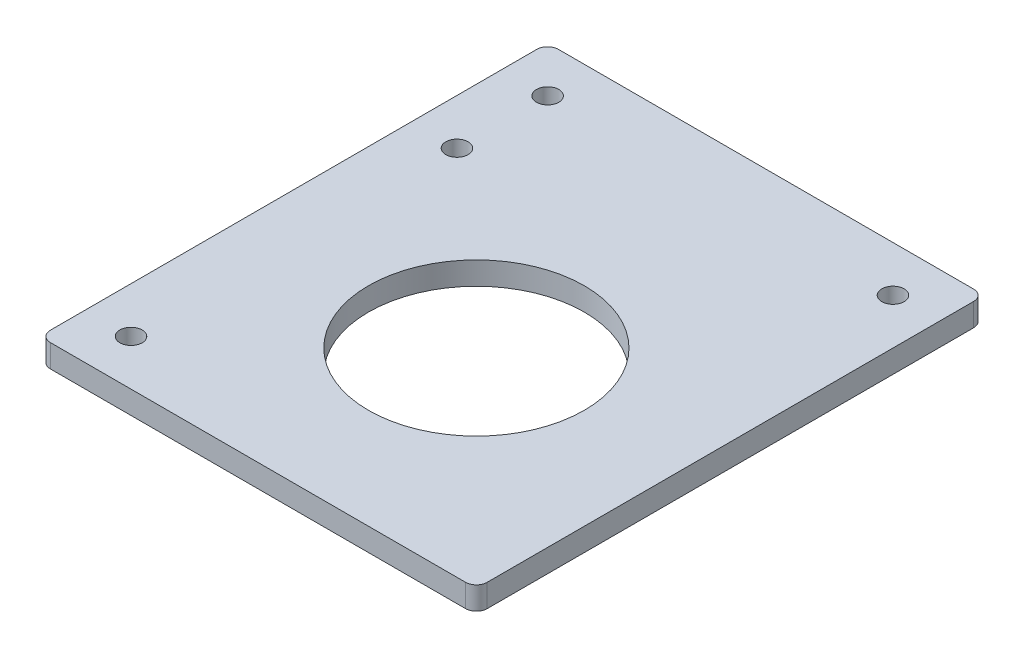
SolidWorks part; units mm, degrees
ref_plane "Front Plane" through (0, 0, 0) normal (0, 0, 1) x (1, 0, 0)
ref_plane "Top Plane" through (0, 0, 0) normal (0, 1, 0) x (1, 0, 0)
ref_plane "Right Plane" through (0, 0, 0) normal (1, 0, 0) x (0, 0, -1)
sketch "Sketch1" plane through (0, 0, 0) normal (0, 1, 0) x (1, 0, 0)
  line L0 (0.7175, -80.6209) -> (93.6586, -80.6209) construction
  line L1 (5.6586, 35.1791) -> (127.0586, 35.1791)
  line L3 (5.6586, -106.0209) -> (127.0586, -106.0209)
  line L4 (127.0586, 35.1791) -> (127.0586, -106.0209)
  line L5 (-22.3414, -80.6209) -> (93.6586, -80.6209) construction
  line L6 (93.6586, -80.6209) -> (101.6586, -72.6209) construction
  line L7 (101.6586, -72.6209) -> (101.6586, -23.6209) construction
  line L12 (101.6586, -23.6209) -> (93.6586, -15.6209) construction
  line L13 (93.6586, -15.6209) -> (0.7175, -15.6209) construction
  line L14 (93.6586, -15.6209) -> (-22.3414, -15.6209) construction
  line L16 (18.3586, 22.4791) -> (5.6586, 22.4791) construction
  line L17 (18.3586, 22.4791) -> (18.3586, 35.1791) construction
  line L18 (114.3586, 22.4791) -> (114.3586, 35.1791) construction
  line L19 (114.3586, 22.4791) -> (127.0586, 22.4791) construction
  line L20 (18.3586, -93.3209) -> (5.6586, -93.3209) construction
  line L21 (18.3586, -93.3209) -> (18.3586, -90.2209) construction
  line L22 (18.3586, -93.3209) -> (18.3586, -106.0209) construction
  line L23 (18.3586, 22.4791) -> (21.4586, 22.4791) construction
  line L24 (5.6586, -26.1209) -> (21.8586, -26.1209) construction
  line L25 (114.3586, 22.4791) -> (114.3586, 19.3791) construction
  line L30 (5.6586, 35.1791) -> (5.6586, -106.0209)
  line L31 (21.8586, -26.1209) -> (-20.3414, -26.1209) construction
  line L32 (18.3586, 22.4791) -> (18.3586, -2.7209) construction
  line L35 (-20.3414, -30.1209) -> (21.8586, -30.1209) construction
  line L36 (5.6586, -30.1209) -> (21.8586, -30.1209) construction
  line L37 (18.3586, -2.7209) -> (21.4586, -2.7209) construction
  circle A0 centre (69.1586, -48.1209) radius 30
  circle A1 centre (18.3586, 22.4791) radius 3.1
  circle A2 centre (114.3586, 22.4791) radius 3.1
  circle A4 centre (18.3586, -93.3209) radius 3.1
  arc A5 (21.8586, -30.1209) -> (21.8586, -26.1209) centre (21.8586, -28.1209) ccw construction
  circle A6 centre (18.3586, -2.7209) radius 3.1
  dimension "D4" = 60
  dimension "D5" = 88
  dimension "D6" = 6.2
  dimension "D1" = 50.8
  dimension "D2" = 25.4
  dimension "D3" = 25.4
  dimension "D7" = 12.7
  dimension "D8" = 25.2
extrude "Boss-Extrude1" add sketch "Sketch1" along normal blind 6.35
fillet "Fillet1" radius 3 4 edges at (127.0586, 3.175, -35.1791) (127.0586, 3.175, 106.0209) (5.6586, 3.175, 106.0209) (5.6586, 3.175, -35.1791)
